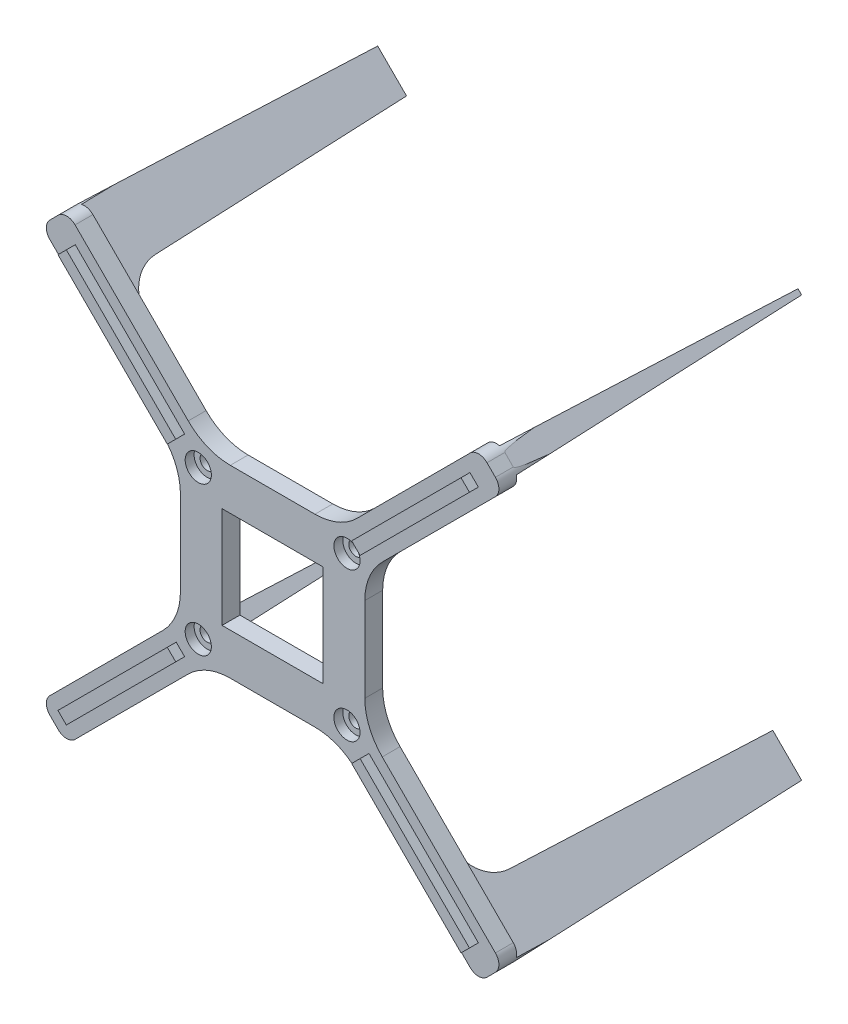
SolidWorks part; units mm, degrees
ref_plane "Front Plane" through (0, 0, 0) normal (1, 0, 0) x (0, 1, 0)
ref_plane "Top Plane" through (0, 0, 0) normal (0, 0, 1) x (0, 1, 0)
ref_plane "Right Plane" through (0, 0, 0) normal (0, 1, 0) x (-1, 0, 0)
sketch "Sketch2" plane through (0, 0, 0) normal (0, 0, 1) x (0, 1, 0)
  line L0 (-15.5, 15.5) -> (-15.5, -15.5) construction
  line L1 (-12, 12) -> (12, 12) construction
  line L2 (-12, 12) -> (-12, -12) construction
  line L3 (-12, -12) -> (12, -12) construction
  line L4 (12, 12) -> (12, -12) construction
  line L5 (-12, 12) -> (12, -12) construction
  line L6 (-12, -12) -> (12, 12) construction
  line L7 (-15.5, -15.5) -> (15.5, -15.5) construction
  line L8 (15.5, 15.5) -> (15.5, -15.5) construction
  line L9 (-15.5, 15.5) -> (15.5, 15.5) construction
  line L10 (-8.5, 8.5) -> (-8.5, -8.5)
  line L11 (-8.5, -8.5) -> (8.5, -8.5)
  line L12 (8.5, 8.5) -> (8.5, -8.5)
  line L13 (-8.5, 8.5) -> (8.5, 8.5)
  line L14 (-12, 12) -> (-36.7487, 36.7487) construction
  line L15 (0, 15.5) -> (0, -15.5) construction
  line L16 (12, 12) -> (36.7487, 36.7487) construction
  line L17 (-15.5, 0) -> (15.5, 0) construction
  line L18 (-12, -12) -> (-36.7487, -36.7487) construction
  line L19 (12, -12) -> (36.7487, -36.7487) construction
  line L20 (-38.8701, 34.6274) -> (-34.6274, 38.8701)
  line L21 (-38.8701, 34.6274) -> (-18.4289, 14.1863)
  line L22 (-34.6274, 38.8701) -> (-14.1863, 18.4289)
  line L23 (38.8701, 34.6274) -> (34.6274, 38.8701)
  line L24 (38.8701, 34.6274) -> (18.4289, 14.1863)
  line L25 (34.6274, 38.8701) -> (14.1863, 18.4289)
  line L26 (-38.8701, -34.6274) -> (-34.6274, -38.8701)
  line L27 (-38.8701, -34.6274) -> (-18.4289, -14.1863)
  line L28 (-34.6274, -38.8701) -> (-14.1863, -18.4289)
  line L29 (38.8701, -34.6274) -> (18.4289, -14.1863)
  line L30 (38.8701, -34.6274) -> (34.6274, -38.8701)
  line L31 (34.6274, -38.8701) -> (14.1863, -18.4289)
  line L32 (-7.1152, 15.5) -> (7.1152, 15.5)
  line L33 (15.5, 7.1152) -> (15.5, -7.1152)
  line L34 (-7.1152, -15.5) -> (7.1152, -15.5)
  line L35 (-15.5, 7.1152) -> (-15.5, -7.1152)
  arc A0 (-18.4289, 14.1863) -> (-15.5, 7.1152) centre (-25.5, 7.1152) cw
  arc A1 (-18.4289, -14.1863) -> (-15.5, -7.1152) centre (-25.5, -7.1152) ccw
  arc A2 (-14.1863, -18.4289) -> (-7.1152, -15.5) centre (-7.1152, -25.5) cw
  arc A3 (14.1863, -18.4289) -> (7.1152, -15.5) centre (7.1152, -25.5) ccw
  arc A4 (18.4289, -14.1863) -> (15.5, -7.1152) centre (25.5, -7.1152) cw
  arc A5 (18.4289, 14.1863) -> (15.5, 7.1152) centre (25.5, 7.1152) ccw
  arc A6 (14.1863, 18.4289) -> (7.1152, 15.5) centre (7.1152, 25.5) cw
  arc A7 (-14.1863, 18.4289) -> (-7.1152, 15.5) centre (-7.1152, 25.5) ccw
  point P0 (0, 0)
  point P25 (-36.7487, 36.7487)
  point P41 (-15.5, 11.2574)
  point P44 (-15.5, -11.2574)
  point P47 (-11.2574, -15.5)
  point P50 (11.2574, -15.5)
  point P53 (15.5, -11.2574)
  point P56 (15.5, 11.2574)
  point P59 (11.2574, 15.5)
  point P62 (-11.2574, 15.5)
  dimension "D7" = 10
  dimension "D1" = 24
  dimension "D4" = 35
  dimension "D5" = 6
  dimension "D6" = 90
  dimension "D2" = 3.5
  dimension "D3" = 3.5
extrude "Boss-Extrude1" add sketch "Sketch2" along normal blind 3
sketch "Sketch3" plane through (0, 0, 3) normal (0, 0, 1) x (1, 0, 0)
  line L1 (-12.5, 12.5) -> (12.5, 12.5) construction
  line L2 (-12.5, 12.5) -> (-12.5, -12.5) construction
  line L3 (-12.5, -12.5) -> (12.5, -12.5) construction
  line L4 (12.5, 12.5) -> (12.5, -12.5) construction
  line L5 (-12.5, 12.5) -> (12.5, -12.5) construction
  line L6 (-12.5, -12.5) -> (12.5, 12.5) construction
  circle A0 centre (-12.5, 12.5) radius 2.2
  circle A1 centre (12.5, 12.5) radius 2.2
  circle A2 centre (12.5, -12.5) radius 2.2
  circle A3 centre (-12.5, -12.5) radius 2.2
  point P0 (0, 0)
  point P7 (11.6907, 12.5)
  point P8 (12, -11.5)
  point P9 (-12, -11.5)
  point P16 (0, 0)
  dimension "D3" = 4.4
  dimension "D1" = 25
  dimension "D2" = 25
  dimension "D4" = 4
extrude "Cut-Extrude1" cut sketch "Sketch3" against normal blind 1.5
sketch "Sketch5" plane through (0, 0, 3) normal (0, 0, 1) x (1, 0, 0)
  line L1 (-12.5, -12.5) -> (12.5, -12.5) construction
  line L2 (-12.5, -12.5) -> (-12.5, 12.5) construction
  line L3 (-12.5, 12.5) -> (12.5, 12.5) construction
  line L4 (12.5, -12.5) -> (12.5, 12.5) construction
  point P1 (12.5, 12.5)
  point P2 (-12.5, -12.5)
  point P3 (-12.5, 12.5)
  point P4 (12.5, -12.5)
  dimension "D1" = 25
hole_wizard "M2 Clearance Hole1" positions "Sketch5" profile "Sketch6" hole size "M2" standard "ISO" end condition through all
sketch "Sketch6" plane through (12.5, 12.5, 3) normal (1, 0, 0) x (0, -1, 0)
  line L0 (0, 0) -> (0, 3)
  line L1 (0, 3) -> (1.2, 3)
  line L2 (1.2, 3) -> (1.2, 0.025)
  line L3 (1.2, 0.025) -> (1.225, 0)
  line L5 (1.225, 0) -> (0, 0)
  line L6 (-1.2, 0.025) -> (-1.225, 0) construction
  line L11 (0, -6.35) -> (0, 107.95) construction
  dimension "Thru Hole Dia." = 2.4
  dimension "Thru Hole Depth" = 3
  dimension "Near C'Sink Dia." = 2.45
  dimension "Near C'Sink Angle" = 90
sketch "Sketch7" plane through (0, 0, 0) normal (0, 0, -1) x (1, 0, 0)
  line L0 (36.7487, 36.7487) -> (29.6777, 29.6777) construction
  line L1 (34.6274, 38.8701) -> (38.8701, 34.6274) construction
  line L2 (28.2635, 31.0919) -> (31.0919, 28.2635)
  line L3 (28.2635, 31.0919) -> (35.3345, 38.163)
  line L4 (31.0919, 28.2635) -> (38.163, 35.3345)
  line L5 (38.163, 35.3345) -> (35.3345, 38.163)
  line L6 (14.1863, 18.4289) -> (34.6274, 38.8701) construction
  line L7 (31.0919, -28.2635) -> (28.2635, -31.0919)
  line L8 (31.0919, -28.2635) -> (38.163, -35.3345)
  line L9 (28.2635, -31.0919) -> (35.3345, -38.163)
  line L10 (35.3345, -38.163) -> (38.163, -35.3345)
  line L11 (36.7487, -36.7487) -> (29.6777, -29.6777) construction
  line L12 (-28.2635, -31.0919) -> (-31.0919, -28.2635)
  line L13 (-28.2635, -31.0919) -> (-35.3345, -38.163)
  line L14 (-31.0919, -28.2635) -> (-38.163, -35.3345)
  line L15 (-38.163, -35.3345) -> (-35.3345, -38.163)
  line L16 (-36.7487, -36.7487) -> (-29.6777, -29.6777) construction
  line L17 (-31.0919, 28.2635) -> (-28.2635, 31.0919)
  line L18 (-31.0919, 28.2635) -> (-38.163, 35.3345)
  line L19 (-28.2635, 31.0919) -> (-35.3345, 38.163)
  line L20 (-35.3345, 38.163) -> (-38.163, 35.3345)
  line L21 (-36.7487, 36.7487) -> (-29.6777, 29.6777) construction
  point P7 (29.6777, 29.6777)
  point P18 (29.6777, -29.6777)
  point P25 (-29.6777, -29.6777)
  point P32 (-29.6777, 29.6777)
  point P35 (0, 0)
  dimension "D1" = 10
  dimension "D2" = 4
  dimension "D3" = 4
extrude "Boss-Extrude2" add sketch "Sketch7" along normal blind 50 draft 1.8
fillet "Fillet1" radius 6 4 edges at (-29.6777, 29.6777, 0) (-29.6777, -29.6777, 0) (29.6777, -29.6777, 0) (29.6777, 29.6777, 0)
fillet "Fillet2" radius 2 8 edges at (-34.6274, 38.8701, 1.5) (-38.8701, 34.6274, 1.5) (-38.8701, -34.6274, 1.5) (-34.6274, -38.8701, 1.5) (34.6274, -38.8701, 1.5) (38.8701, -34.6274, 1.5) (38.8701, 34.6274, 1.5) (34.6274, 38.8701, 1.5)
sketch "Sketch8" plane through (0, 0, 3) normal (0, 0, 1) x (1, 0, 0)
  line L0 (-36.7487, 36.7487) -> (-12.5, 12.5) construction
  line L1 (-36.0416, 37.4558) -> (-37.4558, 36.0416) construction
  line L2 (-7.1152, 15.5) -> (-15.5, 15.5) construction
  line L3 (-16.2071, 14.7929) -> (-14.7929, 16.2071)
  line L4 (-16.2071, 14.7929) -> (-34.5919, 33.1777)
  line L5 (-14.7929, 16.2071) -> (-33.1777, 34.5919)
  line L6 (-33.1777, 34.5919) -> (-34.5919, 33.1777)
  line L7 (14.7929, 16.2071) -> (16.2071, 14.7929)
  line L8 (14.7929, 16.2071) -> (33.1777, 34.5919)
  line L9 (16.2071, 14.7929) -> (34.5919, 33.1777)
  line L10 (34.5919, 33.1777) -> (33.1777, 34.5919)
  line L11 (36.7487, 36.7487) -> (12.5, 12.5) construction
  line L12 (16.2071, -14.7929) -> (14.7929, -16.2071)
  line L13 (16.2071, -14.7929) -> (34.5919, -33.1777)
  line L14 (14.7929, -16.2071) -> (33.1777, -34.5919)
  line L15 (33.1777, -34.5919) -> (34.5919, -33.1777)
  line L16 (36.7487, -36.7487) -> (12.5, -12.5) construction
  line L17 (-14.7929, -16.2071) -> (-16.2071, -14.7929)
  line L18 (-14.7929, -16.2071) -> (-33.1777, -34.5919)
  line L19 (-16.2071, -14.7929) -> (-34.5919, -33.1777)
  line L20 (-34.5919, -33.1777) -> (-33.1777, -34.5919)
  line L21 (-36.7487, -36.7487) -> (-12.5, -12.5) construction
  point P11 (-15.5, 15.5)
  point P20 (15.5, 15.5)
  point P27 (15.5, -15.5)
  point P34 (-15.5, -15.5)
  point P37 (0, 0)
  dimension "D1" = 90
  dimension "D2" = 2
  dimension "D3" = 26
  dimension "D4" = 4
extrude "Boss-Extrude3" add sketch "Sketch8" along normal blind 1.5
